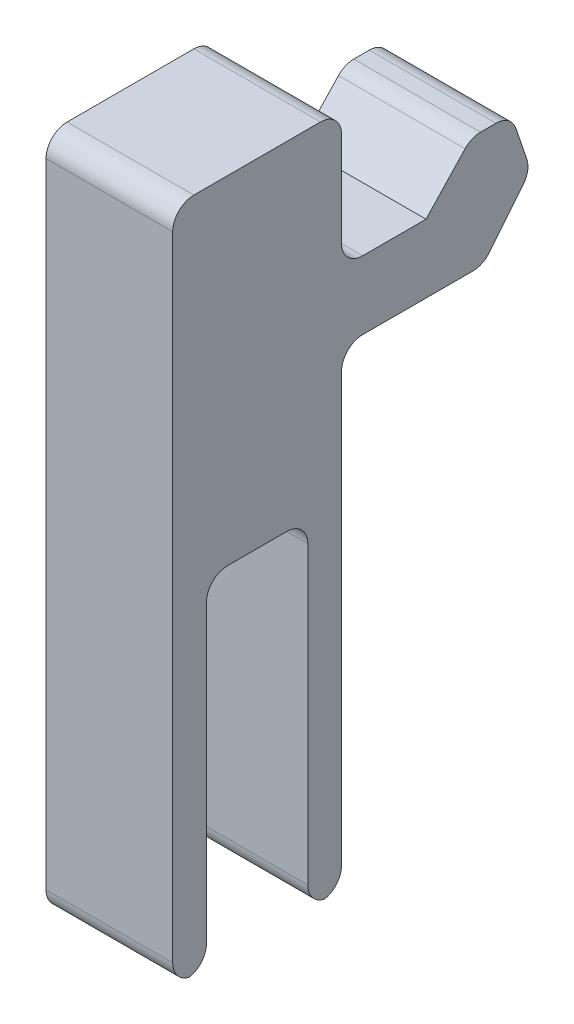
SolidWorks part; units mm, degrees
ref_plane "Alzado" through (0, 0, 0) normal (0, 0, 1) x (1, 0, 0)
ref_plane "Planta" through (0, 0, 0) normal (0, 1, 0) x (1, 0, 0)
ref_plane "Vista lateral" through (0, 0, 0) normal (1, 0, 0) x (0, 0, -1)
sketch "Croquis1" plane through (0, 0, 0) normal (1, 0, 0) x (0, 0, -1)
  line L1 (-2, 8) -> (2, 8)
  line L2 (-2, 8) -> (-2, -8)
  line L3 (-2, -8) -> (2, -8)
  line L16 (2, 8) -> (2, -8)
  dimension "D1" = 2
  dimension "D2" = 8
  dimension "D3" = 16
  dimension "D4" = 4
extrude "Saliente-Extruir1" add sketch "Croquis1" along normal blind 3
sketch "Croquis2" plane through (3, 0, 0) normal (1, 0, 0) x (0, 0, -1)
  line L0 (0, 0) -> (0, -9.3656) construction
  line L1 (-2, -8) -> (2, -8) construction
  line L2 (-1.2, -8) -> (1.2, -8)
  line L3 (-1.2, -8) -> (-1.2, 0)
  line L4 (-1.2, 0) -> (1.2, 0)
  line L5 (1.2, -8) -> (1.2, 0)
  dimension "D1" = 1.2
  dimension "D2" = 1.2
  dimension "D3" = 8
extrude "Cortar-Extruir1" cut sketch "Croquis2" against normal up to surface (3 mm away) up to face at (0, 0, 0)
sketch "Croquis4" plane through (3, 0, 0) normal (1, 0, 0) x (0, 0, -1)
  line L0 (2, 4.7559) -> (4, 4.7559)
  line L2 (2, -8) -> (2, 8) construction
  line L9 (1.2, 0) -> (-1.2, 0) construction
  line L10 (0, 0) -> (0, 10.8389) construction
  line L11 (4, 4.7559) -> (5.0744, 5.8963)
  line L12 (5.0744, 5.8963) -> (6.0144, 5.8963)
  line L13 (6.0144, 5.8963) -> (6.4764, 4.5311)
  line L14 (6.4764, 4.5311) -> (5.3503, 3.1377)
  line L15 (5.3503, 3.1377) -> (2, 3.1377)
  line L16 (2, 4.7559) -> (2, 3.1377)
  dimension "D1" = 3.1377
  dimension "D2" = 4.7559
  dimension "D3" = 5.8963
  dimension "D4" = 2
extrude "Saliente-Extruir2" add sketch "Croquis4" against normal up to surface (3 mm away) up to face at (0, -2, 0)
fillet "Redondeo2" radius 0.5 14 edges at (1.5, 5.8963, -5.0744) (1.5, 5.8963, -6.0144) (1.5, 4.5311, -6.4764) (1.5, 3.1377, -2) (1.5, 3.1377, -5.3503) (1.5, 4.7559, -2) (1.5, 8, -2) (1.5, 8, 2) (1.5, 0, 1.2) (1.5, 0, -1.2) (1.5, -8, 2) (1.5, -8, -1.2) (1.5, -8, -2) (1.5, -8, 1.2)
